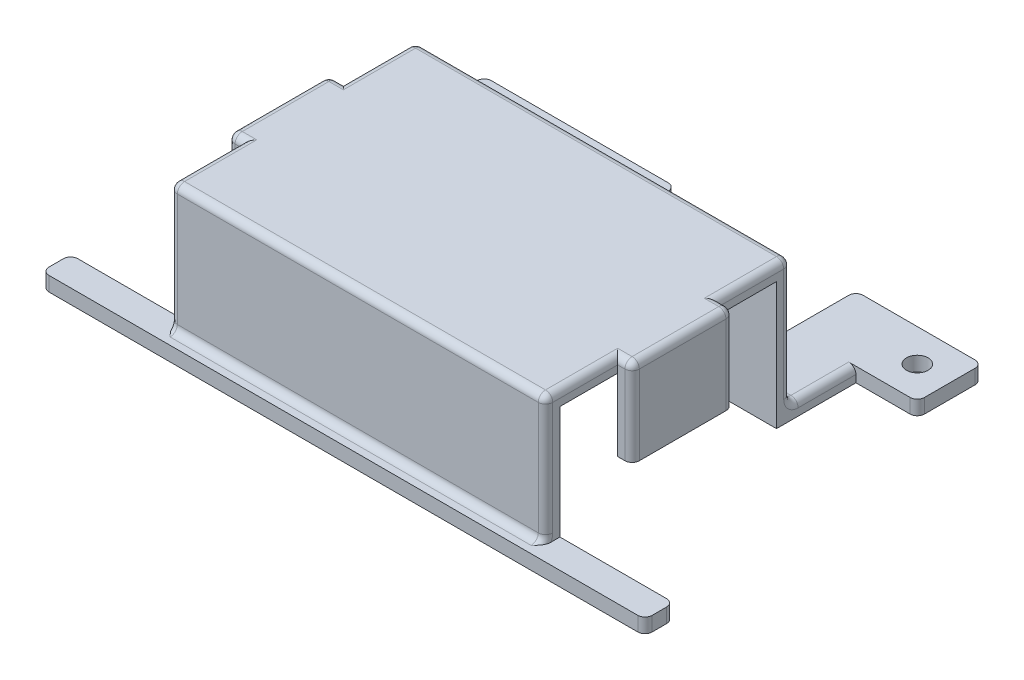
SolidWorks part; units mm, degrees
ref_plane "Front Plane" through (0, 0, 0) normal (0, 0, 1) x (1, 0, 0)
ref_plane "Top Plane" through (0, 0, 0) normal (0, 1, 0) x (1, 0, 0)
ref_plane "Right Plane" through (0, 0, 0) normal (1, 0, 0) x (0, 0, -1)
sketch "Sketch1" plane through (0, 0, 0) normal (0, 1, 0) x (1, 0, 0)
  line L1 (0, 0) -> (52, 0)
  line L2 (0, 0) -> (0, 34)
  line L3 (0, 34) -> (52, 34)
  line L4 (52, 0) -> (52, 34)
  dimension "D1" = 52
  dimension "D2" = 34
extrude "Boss-Extrude1" add sketch "Sketch1" along normal blind 19.65
sketch "Sketch2" plane through (0, 0, 0) normal (0, -1, 0) x (-1, 0, 0)
  line L0 (-52, 0) -> (-52, 34) construction
  line L1 (-52, 2) -> (0, 2)
  line L2 (-52, 2) -> (-52, 32)
  line L3 (-52, 32) -> (0, 32)
  line L4 (0, 2) -> (0, 32)
  line L5 (0, 34) -> (0, 0) construction
  line L6 (0, 0) -> (-52, 0) construction
  line L7 (-52, 34) -> (0, 34) construction
  dimension "D1" = 2
  dimension "D2" = 2
extrude "Cut-Extrude1" cut sketch "Sketch2" against normal blind 17.65
sketch "Sketch3" plane through (0, 0, -34) normal (0, 0, -1) x (-1, 0, 0)
  line L1 (-52, 0) -> (-43, 0)
  line L2 (-52, 0) -> (-52, 2)
  line L3 (-52, 2) -> (-43, 2)
  line L4 (-43, 0) -> (-43, 2)
  line L5 (0, 0) -> (-18, 0)
  line L6 (0, 0) -> (0, 2)
  line L7 (0, 2) -> (-18, 2)
  line L8 (-18, 0) -> (-18, 2)
  dimension "D1" = 9
  dimension "D2" = 2
  dimension "D3" = 18
  dimension "D4" = 2
extrude "Boss-Extrude2" add sketch "Sketch3" along normal blind 18
sketch "Sketch4" plane through (52, 0, 0) normal (1, 0, 0) x (0, 0, -1)
  line L0 (52, 2) -> (52, 0) construction
  line L1 (34, 2) -> (52, 2)
  line L2 (34, 2) -> (34, 0)
  line L3 (34, 0) -> (52, 0)
  line L4 (52, 2) -> (52, 0)
  line L5 (32, 0) -> (52, 0) construction
extrude "Boss-Extrude3" add sketch "Sketch4" along normal blind 8.5
sketch "Sketch5" plane through (0, 0, 0) normal (-1, 0, 0) x (0, 0, 1)
  line L1 (-34, 2) -> (-52, 2)
  line L2 (-34, 2) -> (-34, 0)
  line L3 (-34, 0) -> (-52, 0)
  line L4 (-52, 2) -> (-52, 0)
extrude "Boss-Extrude4" add sketch "Sketch5" along normal blind 8.5
sketch "Sketch6" plane through (0, 2, 0) normal (0, 1, 0) x (1, 0, 0)
  line L0 (-8.5, 34) -> (-8.5, 52) construction
  line L1 (-8.5, 52) -> (18, 52) construction
  line L2 (43, 52) -> (60.5, 52) construction
  line L3 (60.5, 52) -> (60.5, 34) construction
  circle A0 centre (56, 47.5) radius 1.5
  circle A1 centre (-4, 47.5) radius 1.5
  dimension "D1" = 3
  dimension "D2" = 3
  dimension "D3" = 4.5
  dimension "D4" = 4.5
  dimension "D5" = 4.5
  dimension "D6" = 4.5
extrude "Cut-Extrude2" cut sketch "Sketch6" against normal through all
sketch "Sketch7" plane through (0, 0, 0) normal (0, 0, 1) x (1, 0, 0)
  line L0 (0, 19.65) -> (0, 0) construction
  line L1 (0, 2) -> (52, 2)
  line L2 (0, 2) -> (0, 0)
  line L3 (0, 0) -> (52, 0)
  line L4 (52, 2) -> (52, 0)
  dimension "D1" = 2
extrude "Boss-Extrude5" add sketch "Sketch7" along normal blind 2
sketch "Sketch8" plane through (0, 0, 0) normal (-1, 0, 0) x (0, 0, 1)
  line L0 (-2, 0) -> (2, 0) construction
  line L1 (2, 2) -> (-2, 2)
  line L2 (2, 2) -> (2, 0)
  line L3 (2, 0) -> (-2, 0)
  line L4 (-2, 2) -> (-2, 0)
extrude "Boss-Extrude6" add sketch "Sketch8" along normal blind 15.78
sketch "Sketch9" plane through (52, 0, 0) normal (1, 0, 0) x (0, 0, -1)
  line L1 (-2, 2) -> (2, 2)
  line L2 (-2, 2) -> (-2, 0)
  line L3 (-2, 0) -> (2, 0)
  line L4 (2, 2) -> (2, 0)
extrude "Boss-Extrude7" add sketch "Sketch9" along normal blind 15.78
sketch "Sketch11" plane through (-8.5, 0, 0) normal (-1, 0, 0) x (0, 0, 1)
  line L1 (-43, 17.65) -> (-32, 17.65)
  line L2 (-43, 17.65) -> (-43, 0)
  line L3 (-43, 0) -> (-32, 0)
  line L4 (-32, 17.65) -> (-32, 0)
  dimension "D1" = 11
  dimension "D2" = 17.65
  dimension "D3" = 9
extrude "Cut-Extrude3" cut sketch "Sketch11" against normal blind 18
sketch "Sketch12" plane through (60.5, 0, 0) normal (1, 0, 0) x (0, 0, -1)
  line L0 (52, 2) -> (34, 2) construction
  line L1 (43, 2) -> (34, 2)
  line L2 (43, 2) -> (43, 0)
  line L3 (43, 0) -> (34, 0)
  line L4 (34, 2) -> (34, 0)
extrude "Cut-Extrude4" cut sketch "Sketch12" against normal blind 8.5
sketch "Sketch14" plane through (0, 0, 0) normal (-1, 0, 0) x (0, 0, 1)
  line L0 (-34, 19.65) -> (0, 19.65) construction
  line L1 (-24, 19.65) -> (-10, 19.65)
  line L2 (-24, 19.65) -> (-24, 17.65)
  line L3 (-24, 17.65) -> (-10, 17.65)
  line L4 (-10, 19.65) -> (-10, 17.65)
  line L5 (-2, 17.65) -> (-34, 17.65) construction
  line L7 (0, 19.65) -> (0, 2) construction
  line L8 (-34, 19.65) -> (-34, 17.65) construction
  point P10 (-10, 18.65)
  point P13 (-34, 18.65)
  dimension "D1" = 10
  dimension "D2" = 10
extrude "Boss-Extrude8" add sketch "Sketch14" along normal blind 2
sketch "Sketch15" plane through (52, 0, 0) normal (1, 0, 0) x (0, 0, -1)
  line L0 (32, 17.65) -> (2, 17.65) construction
  line L1 (24, 17.65) -> (10, 17.65)
  line L2 (24, 17.65) -> (24, 19.65)
  line L3 (24, 19.65) -> (10, 19.65)
  line L4 (10, 17.65) -> (10, 19.65)
  line L5 (0, 19.65) -> (34, 19.65) construction
  line L6 (34, 19.65) -> (34, 2) construction
  dimension "D1" = 10
  dimension "D2" = 10
extrude "Boss-Extrude9" add sketch "Sketch15" along normal blind 2
sketch "Sketch16" plane through (0, 17.65, 0) normal (0, -1, 0) x (-1, 0, 0)
  line L1 (0, 24) -> (2, 24)
  line L2 (0, 24) -> (0, 10)
  line L3 (0, 10) -> (2, 10)
  line L4 (2, 24) -> (2, 10)
  line L5 (-52, 24) -> (-54, 24)
  line L6 (-52, 24) -> (-52, 10)
  line L7 (-52, 10) -> (-54, 10)
  line L8 (-54, 24) -> (-54, 10)
extrude "Boss-Extrude10" add sketch "Sketch16" along normal blind 10
fillet "Fillet1" radius 1 7 edges at (43, 1, -34) (18, 1, -34) (47.5, 2, -34) (13.75, 2, -34) (26, 19.65, -34) (26, 2, 0) (26, 19.65, 0)
fillet "Fillet2" radius 1 23 edges at (9.5, 2, -39) (9.5, 2.2929, -34.2929) (0, 18.15, -34) (0, 19.3571, -33.7071) (0, 2.2929, 0.2929) (0, 10.825, 0) (0, 19.3571, -0.2929) (52, 2, -39) (52, 2.2929, -34.2929) (52, 10.825, -34) (52, 19.3571, -33.7071) (52, 2.2929, 0.2929) (52, 10.825, 0) (52, 19.3571, -0.2929) (9.5, 10.325, -34) (-1, 19.65, -24) (0, 19.65, -28.5) (-1, 19.65, -10) (0, 19.65, -5.5) (53, 19.65, -24) (52, 19.65, -28.5) (53, 19.65, -10) (52, 19.65, -5.5)
fillet "Fillet3" radius 1 10 edges at (-2, 13.15, -10) (-2, 19.3571, -10.2929) (-2, 19.65, -17) (-2, 19.3571, -23.7071) (54, 13.15, -24) (54, 19.3571, -23.7071) (54, 19.65, -17) (54, 19.3571, -10.2929) (-2, 13.15, -24) (54, 13.15, -10)
fillet "Fillet4" radius 1 10 edges at (67.78, 1, -2) (67.78, 1, 2) (-15.78, 1, -2) (-15.78, 1, 2) (-8.5, 1, -52) (-8.5, 1, -43) (60.5, 1, -52) (60.5, 1, -43) (43, 1, -52) (18, 1, -52)
